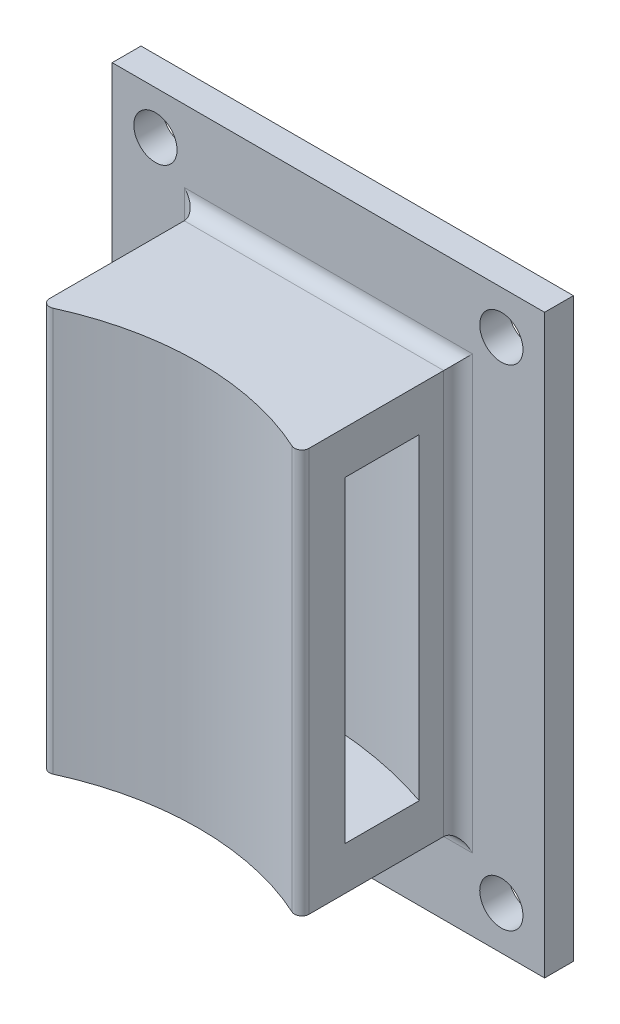
SolidWorks part; units mm, degrees
ref_plane "前视基准面" through (0, 0, 0) normal (0, 0, 1) x (1, 0, 0)
ref_plane "上视基准面" through (0, 0, 0) normal (0, 1, 0) x (1, 0, 0)
ref_plane "右视基准面" through (0, 0, 0) normal (1, 0, 0) x (0, 0, -1)
sketch "草图1" plane through (0, 0, 0) normal (0, 1, 0) x (1, 0, 0)
  line L0 (-9, 31) -> (-9, 26.3029)
  line L1 (0, -1000) -> (0, 49000) construction
  line L2 (9, 31) -> (9, 26.3029)
  line L3 (-9, 31) -> (9, 31)
  line L4 (-9, 21.166) -> (-9, 17.8606)
  line L5 (9, 21.166) -> (9, 17.8606)
  arc A0 (9, 17.8606) -> (-9, 17.8606) centre (0, 0) ccw
  arc A1 (9, 21.166) -> (-9, 21.166) centre (0, 0) ccw
  arc A2 (9, 26.3029) -> (-9, 26.3029) centre (0, 0) ccw
  circle A3 centre (0, 0) radius 27.8 construction
  circle A4 centre (0, 0) radius 23 construction
  circle A5 centre (0, 0) radius 20 construction
  dimension "D1" = 40
  dimension "D4" = 18
  dimension "D5" = 31
  dimension "D2" = 3
  dimension "D3" = 4.8
extrude "凸台-拉伸1" add sketch "草图1" along normal mid plane 22
sketch "草图2" plane through (0, 11, 0) normal (0, 1, 0) x (1, 0, 0)
  line L0 (-9, 31) -> (-9, 17.8606)
  line L2 (9, 17.8606) -> (9, 21.166)
  line L3 (9, 31) -> (-9, 31)
  line L4 (-9, 31) -> (-9, 26.3029)
  line L5 (9, 26.3029) -> (9, 31)
  line L6 (9, 31) -> (-9, 31)
  line L9 (-9, 21.166) -> (-9, 17.8606)
  line L12 (9, 17.8606) -> (9, 31)
  arc A1 (9, 26.3029) -> (-9, 26.3029) centre (0, 0) ccw
  arc A4 (9, 17.8606) -> (-9, 17.8606) centre (0, 0) ccw
  arc A5 (9, 21.166) -> (-9, 21.166) centre (0, 0) ccw
  arc A6 (9, 17.8606) -> (-9, 17.8606) centre (0, 0) ccw
  dimension "D1" = 0
  dimension "D2" = 0
extrude "凸台-拉伸2" add sketch "草图2" along normal blind 3
mirror "镜向1" about plane through (0, 0, 0) normal (0, 1, 0) of "凸台-拉伸2"
sketch "草图5" plane through (0, 0, -31) normal (0, 0, -1) x (-1, 0, 0)
  line L8 (-9, 14) -> (-9, -14)
  line L9 (-9, -14) -> (9, -14)
  line L10 (9, -14) -> (9, 14)
  line L11 (9, 14) -> (-9, 14)
  line L12 (-9, 14) -> (-9, -14)
  line L13 (-9, -14) -> (9, -14)
  line L14 (9, -14) -> (9, 14)
  line L15 (9, 14) -> (-9, 14)
  line L20 (-15, 20) -> (-15, -20)
  line L21 (-15, -20) -> (15, -20)
  line L22 (15, -20) -> (15, 20)
  line L23 (15, 20) -> (-15, 20)
  line L24 (-15, 20) -> (-15, -20)
  line L25 (-15, -20) -> (15, -20)
  line L26 (15, -20) -> (15, 20)
  line L27 (15, 20) -> (-15, 20)
  dimension "D1" = 0
  dimension "D2" = 6
extrude "凸台-拉伸3" add sketch "草图5" against normal blind 2
sketch "草图6" plane through (0, 0, -29) normal (0, 0, 1) x (1, 0, 0)
  line L0 (15, 20) -> (15, -20) construction
  line L1 (-15, 20) -> (15, 20) construction
  line L2 (0, 20) -> (0, -20) construction
  line L3 (15, -20) -> (-15, -20) construction
  line L4 (-15, 0) -> (15, 0) construction
  line L5 (-15, -20) -> (-15, 20) construction
  circle A0 centre (12, 17) radius 1.5
  circle A1 centre (-12, 17) radius 1.5
  circle A2 centre (12, -17) radius 1.5
  circle A3 centre (-12, -17) radius 1.5
  dimension "D1" = 3
  dimension "D2" = 24
  dimension "D3" = 34
extrude "切除-拉伸1" cut sketch "草图6" against normal through all
fillet "圆角1" radius 1 4 edges at (9, 0, -29) (0, 14, -29) (-9, 0, -29) (0, -14, -29)
fillet "圆角2" radius 0.5 2 edges at (9, 0, -17.8606) (-9, 0, -17.8606)
